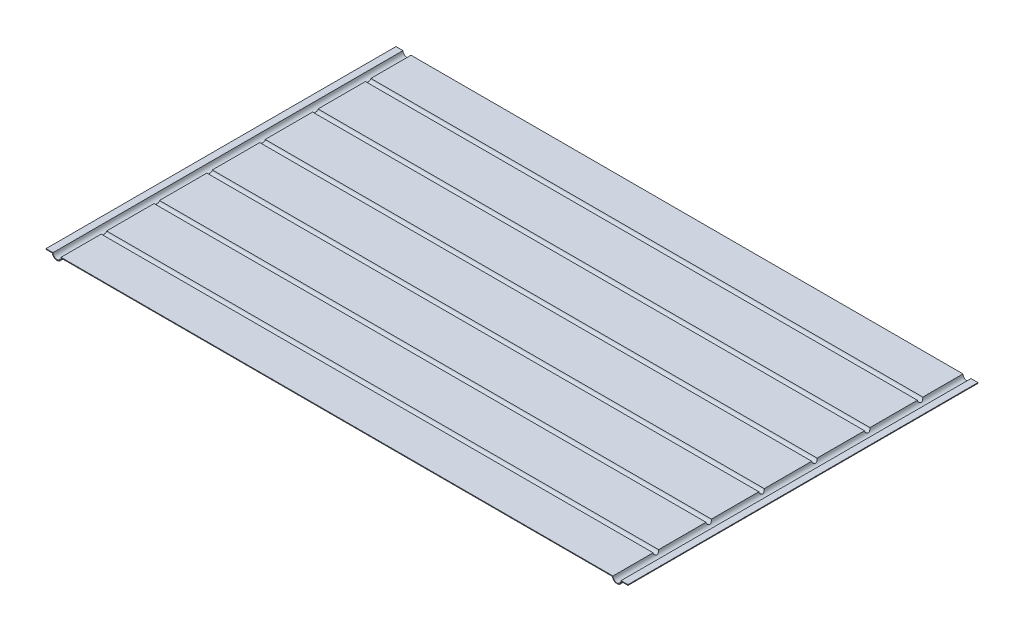
SolidWorks part; units mm, degrees
material "Titanium"
ref_plane "Front Plane" through (0, 0, 0) normal (0, 0, 1) x (1, 0, 0)
ref_plane "Top Plane" through (0, 0, 0) normal (0, 1, 0) x (1, 0, 0)
ref_plane "Right Plane" through (0, 0, 0) normal (1, 0, 0) x (0, 0, -1)
sketch "Sketch1" plane through (0, 0, 0) normal (0, 0, 1) x (1, 0, 0)
  line L0 (11.45, 0) -> (1587.55, 0)
  line L1 (-11.45, 0) -> (-12.45, 0)
  line L3 (13.3005, -2) -> (1586.6995, -2)
  line L6 (1611.45, 0) -> (1613.45, 0)
  line L7 (1588.55, 0) -> (1587.55, 0)
  line L10 (-13.3005, -2) -> (-31.45, -2)
  line L11 (-31.45, -2) -> (-31.45, 0)
  line L12 (-31.45, 0) -> (-12.45, 0)
  line L15 (1613.45, -2) -> (1631.45, -2)
  line L16 (1631.45, -2) -> (1631.45, 0)
  line L17 (1631.45, 0) -> (1613.45, 0)
  line L18 (1613.45, -2) -> (1613.3005, -2)
  arc A0 (-11.45, 0) -> (11.45, 0) centre (0, 0) ccw
  arc A1 (1588.55, 0) -> (1611.45, 0) centre (1600, 0) ccw
  arc A2 (-13.3005, -2) -> (13.3005, -2) centre (0, 0) ccw
  arc A3 (1586.6995, -2) -> (1613.3005, -2) centre (1600, 0) ccw
  dimension "D1" = 22.9
  dimension "D2" = 22.9
  dimension "D4" = 26.9
  dimension "D5" = 26.9
  dimension "D3" = 1600
  dimension "D6" = 2
  dimension "D7" = 20
  dimension "D8" = 20
  dimension "D9" = 13.45
extrude "Boss-Extrude1" add sketch "Sketch1" along normal blind 1000
sketch "Sketch2" plane through (-31.45, 0, 0) normal (-1, 0, 0) x (0, 0, 1)
  line L0 (1000, 0) -> (0, 0) construction
  circle A0 centre (122.5, 0) radius 7.75
  circle A1 centre (273.5, 0) radius 7.75
  circle A2 centre (424.5, 0) radius 7.75
  circle A3 centre (575.5, 0) radius 7.75
  circle A4 centre (726.5, 0) radius 7.75
  circle A5 centre (877.5, 0) radius 7.75
  dimension "D1" = 15.5
  dimension "D2" = 122.5
extrude "Cut-Extrude1" cut sketch "Sketch2" against normal through all
sketch "Sketch4" plane through (0, -2, 0) normal (0, -1, 0) x (1, 0, 0)
  line L0 (800, 1000) -> (800, 0) construction
  line L1 (13.3005, 1000) -> (1586.6995, 1000) construction
  line L2 (13.3005, 0) -> (1586.6995, 0) construction
ref_plane "Plane1" through (800, 0, 0) normal (1, 0, 0) x (0, 0, -1)
sketch "Sketch5" plane through (800, 0, 0) normal (1, 0, 0) x (0, 0, -1)
  line L1 (-887.25, 0) -> (-885.25, 0)
  line L2 (-869.75, 0) -> (-867.75, 0)
  line L3 (-718.75, 0) -> (-716.75, 0)
  line L4 (-736.25, 0) -> (-734.25, 0)
  line L5 (-567.75, 0) -> (-565.75, 0)
  line L6 (-585.25, 0) -> (-583.25, 0)
  line L7 (-416.75, 0) -> (-414.75, 0)
  line L8 (-434.25, 0) -> (-432.25, 0)
  line L9 (-265.75, 0) -> (-263.75, 0)
  line L10 (-283.25, 0) -> (-281.25, 0)
  line L11 (-114.75, 0) -> (-112.75, 0)
  line L12 (-132.25, 0) -> (-130.25, 0)
  arc A0 (-885.25, 0) -> (-869.75, 0) centre (-877.5, 0) ccw
  arc A1 (-887.25, 0) -> (-867.75, 0) centre (-877.5, 0) ccw
  arc A2 (-734.25, 0) -> (-718.75, 0) centre (-726.5, 0) ccw
  arc A3 (-736.25, 0) -> (-716.75, 0) centre (-726.5, 0) ccw
  arc A4 (-583.25, 0) -> (-567.75, 0) centre (-575.5, 0) ccw
  arc A5 (-585.25, 0) -> (-565.75, 0) centre (-575.5, 0) ccw
  arc A6 (-432.25, 0) -> (-416.75, 0) centre (-424.5, 0) ccw
  arc A7 (-434.25, 0) -> (-414.75, 0) centre (-424.5, 0) ccw
  arc A8 (-281.25, 0) -> (-265.75, 0) centre (-273.5, 0) ccw
  arc A9 (-283.25, 0) -> (-263.75, 0) centre (-273.5, 0) ccw
  arc A10 (-130.25, 0) -> (-114.75, 0) centre (-122.5, 0) ccw
  arc A11 (-132.25, 0) -> (-112.75, 0) centre (-122.5, 0) ccw
  dimension "D2" = 19.5
extrude "Boss-Extrude2" add sketch "Sketch5" along normal up to surface and the other way up to surface up to face at (1600.0006, -5.2811, 499.9565) other way up to face at (0.0006, -5.2811, 499.9565)
sketch "Sketch6" plane through (1631.45, 0, 0) normal (1, 0, 0) x (0, 0, -1)
  line L3 (-130.25, 0) -> (-114.75, 0)
  line L4 (-281.25, 0) -> (-265.75, 0)
  line L5 (-432.25, 0) -> (-416.75, 0)
  line L6 (-583.25, 0) -> (-567.75, 0)
  line L7 (-734.25, 0) -> (-718.75, 0)
  line L8 (-885.25, 0) -> (-869.75, 0)
  arc A0 (-130.25, 0) -> (-114.75, 0) centre (-122.5, 0) ccw
  arc A1 (-281.25, 0) -> (-265.75, 0) centre (-273.5, 0) ccw
  arc A2 (-432.25, 0) -> (-416.75, 0) centre (-424.5, 0) ccw
  arc A3 (-583.25, 0) -> (-567.75, 0) centre (-575.5, 0) ccw
  arc A4 (-734.25, 0) -> (-718.75, 0) centre (-726.5, 0) ccw
  arc A5 (-885.25, 0) -> (-869.75, 0) centre (-877.5, 0) ccw
  dimension "D1" = 6
extrude "Boss-Extrude4" add sketch "Sketch6" against normal up to surface (20 mm away) up to face at (1600, -4.1333, 500)
sketch "Sketch7" plane through (0, 0, 0) normal (0, 0, -1) x (-1, 0, 0)
  line L0 (-1613.3005, -2) -> (-1631.45, -2)
  line L1 (-1631.45, -2) -> (-1631.45, -7.75)
  line L2 (-1631.45, -7.75) -> (-1610.9927, -7.75)
  line L3 (-800, 550) -> (-800, -550) construction
  line L4 (13.3005, -2) -> (31.45, -2)
  line L5 (31.45, -2) -> (31.45, -7.75)
  line L6 (31.45, -7.75) -> (10.9927, -7.75)
  arc A0 (-1613.3005, -2) -> (-1586.6995, -2) centre (-1600, 0) ccw construction
  arc A1 (-1613.3005, -2) -> (-1610.9927, -7.75) centre (-1600, 0) ccw
  arc A2 (13.3005, -2) -> (10.9927, -7.75) centre (0, 0) cw
extrude "Cut-Extrude2" cut sketch "Sketch7" against normal through all
sketch "Sketch8" plane through (-31.45, 0, 0) normal (-1, 0, 0) x (0, 0, 1)
  line L0 (130.25, 0) -> (114.75, 0)
  line L1 (281.25, 0) -> (265.75, 0)
  line L2 (432.25, 0) -> (416.75, 0)
  line L3 (583.25, 0) -> (567.75, 0)
  line L4 (734.25, 0) -> (718.75, 0)
  line L5 (885.25, 0) -> (869.75, 0)
  arc A0 (114.75, 0) -> (130.25, 0) centre (122.5, 0) ccw
  arc A1 (265.75, 0) -> (281.25, 0) centre (273.5, 0) ccw
  arc A2 (416.75, 0) -> (432.25, 0) centre (424.5, 0) ccw
  arc A3 (567.75, 0) -> (583.25, 0) centre (575.5, 0) ccw
  arc A4 (718.75, 0) -> (734.25, 0) centre (726.5, 0) ccw
  arc A5 (869.75, 0) -> (885.25, 0) centre (877.5, 0) ccw
extrude "Boss-Extrude5" add sketch "Sketch8" against normal up to surface (20 mm away) up to face at (0, -0.8179, 500.1988)
extrude "Cut-Extrude3" cut sketch "Sketch7<2>" against normal through all
sketch "Sketch7<2>" plane through (0, 0, 0) normal (0, 0, -1) x (-1, 0, 0) same geometry as "Sketch7"
